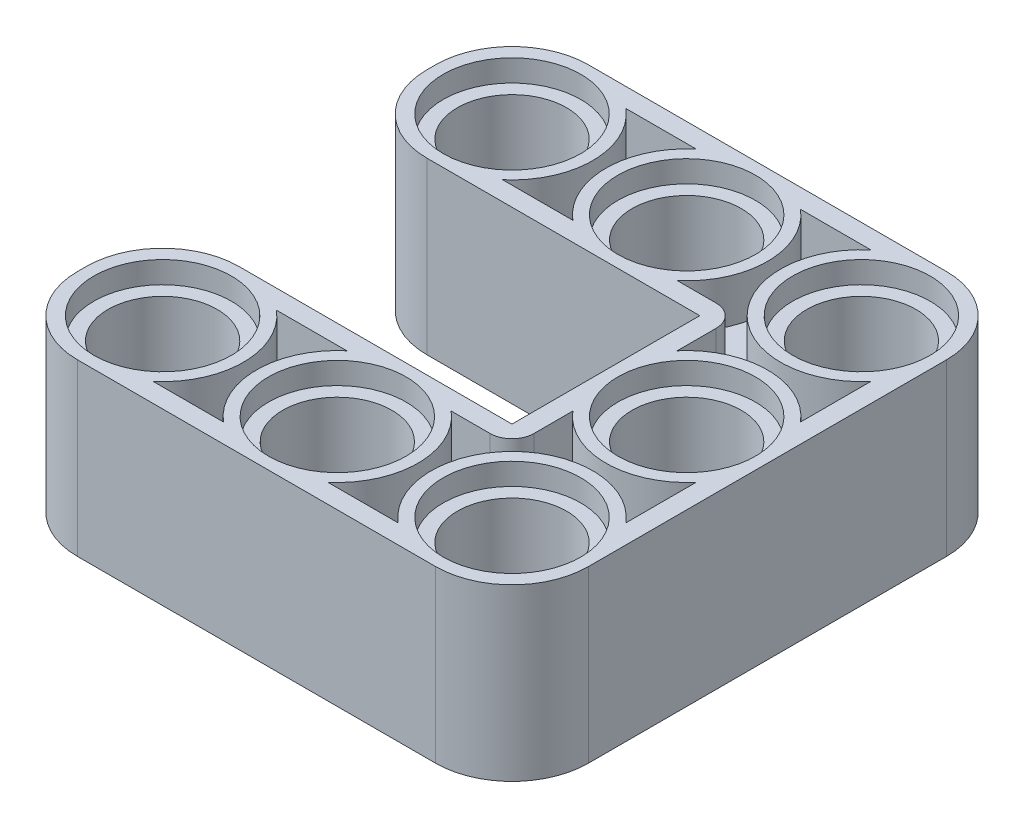
SolidWorks part; units mm, degrees
note: The reader was unsure of these and kept them because the rebuilt part matched: shared geometry of "草图1<3>", "草图1<4>", "草图1<5>", "草图3<3>", "草图3<4>", "草图3<5>".
ref_plane "前视基准面" through (0, 0, 0) normal (0, 0, 1) x (1, 0, 0)
ref_plane "上视基准面" through (0, 0, 0) normal (0, 1, 0) x (1, 0, 0)
ref_plane "右视基准面" through (0, 0, 0) normal (1, 0, 0) x (0, 0, -1)
other "Configuration Table"
sketch "草图1" plane through (0, 0, 0) normal (0, 1, 0) x (1, 0, 0)
  line L0 (-23.4, 8) -> (0, 8) construction
  line L1 (-23.4, 11.7) -> (0, 11.7)
  line L2 (-23.4, 11.7) -> (-23.4, 4.3)
  line L3 (-23.4, 4.3) -> (0, 4.3)
  line L4 (0, 11.7) -> (0, 4.3)
  line L5 (-7.4, 4.3) -> (0, 4.3)
  line L6 (-7.4, 4.3) -> (-7.4, -4.3)
  line L7 (-7.4, -4.3) -> (0, -4.3)
  line L8 (0, 4.3) -> (0, -4.3)
  line L9 (0, -4.3) -> (-23.4, -4.3)
  line L10 (0, -4.3) -> (0, -11.7)
  line L11 (0, -11.7) -> (-23.4, -11.7)
  line L12 (-23.4, -4.3) -> (-23.4, -11.7)
  line L13 (-7.4, 0) -> (0, 0) construction
  line L14 (-3.7, 0) -> (-3.7, 11.7) construction
  circle A0 centre (-3.7, 8) radius 2.5
  circle A1 centre (-3.7, 8) radius 3.15
  circle A2 centre (-3.7, 8) radius 3.7
  dimension "D5" = 7.4
  dimension "D6" = 6.3
  dimension "D7" = 5
  dimension "D1" = 8
  dimension "D2" = 23.4
  dimension "D3" = 7.4
  dimension "D4" = 23.4
extrude "凸台-拉伸1" add sketch "草图1" along normal blind 7.8 contours L9 L12 L11 L10 L7 | L8 L5 L3 L6 L7
extrude "切除-拉伸1" cut sketch "草图1<3>" along normal up to next contours A0
sketch "草图1<3>" plane through (0, 0, 0) normal (0, 1, 0) x (1, 0, 0) same geometry as "草图1"
extrude "切除-拉伸2" cut sketch "草图1<4>" along normal blind 1 contours A1 A0
sketch "草图1<4>" plane through (0, 0, 0) normal (0, 1, 0) x (1, 0, 0) same geometry as "草图1"
extrude "切除-拉伸3" cut sketch "草图1<5>" against normal blind 1 from surface at 7.8 contours A1 A0 starting at face at (-3.7, 7.8, -5.5)
sketch "草图1<5>" plane through (0, 0, 0) normal (0, 1, 0) x (1, 0, 0) same geometry as "草图1"
pattern_linear "阵列(线性)3" count 3 spacing 8 along (-1, 0, 0) of "切除-拉伸1", "切除-拉伸2", "切除-拉伸3"
pattern_linear "阵列(线性)4" count 3 spacing 8 along (0, 0, 1) of "切除-拉伸1", "切除-拉伸2", "切除-拉伸3"
pattern_linear "阵列(线性)5" count 2 spacing 16 along (0, 0, 1) of "阵列(线性)3"
sketch "草图3" plane through (0, 0, 0) normal (0, -1, 0) x (1, 0, 0)
  line L0 (-7.4, 0) -> (0, 0) construction
  line L1 (-7.4, -4.3) -> (-7.4, 4.3) construction
  line L2 (-3.7, 0) -> (-3.7, 11.7) construction
  line L3 (0, 11.7) -> (-23.4, 11.7) construction
  line L4 (-23.4, 8) -> (0, 8) construction
  line L5 (-23.4, 4.3) -> (-23.4, 11.7) construction
  line L6 (0, -11.7) -> (0, 11.7) construction
  line L7 (-3.7, 11.15) -> (-3.7, 10.5)
  line L8 (-3.7, 5.5) -> (-3.7, 4.85)
  line L9 (-3.7, 10.825) -> (-9.3106, 10.825)
  line L10 (-3.7, 5.175) -> (-9.3106, 5.175)
  line L11 (-6.85, 8) -> (-6.2, 8)
  line L12 (-1.2, 8) -> (-0.55, 8)
  line L13 (-0.875, 8) -> (-0.875, 2.3894)
  line L14 (-6.525, 8) -> (-6.525, 2.3894)
  circle A0 centre (-3.7, 8) radius 3.7
  circle A1 centre (-3.7, 8) radius 3.15
  circle A2 centre (-3.7, 8) radius 2.5
  circle A3 centre (-3.7, 0) radius 3.7
  circle A4 centre (-11.7, 8) radius 3.7
  dimension "D2" = 7.4
  dimension "D3" = 6.3
  dimension "D4" = 5
  dimension "D1" = 8
extrude "切除-拉伸4" cut sketch "草图3" against normal blind 2 contours A4 L10 L14 A0 L9 | A0 L14 L10
extrude "切除-拉伸5" cut sketch "草图3<3>" along normal blind 2 from surface at -7.8 contours A4 L10 L14 A0 L9 | A0 L14 L10 starting at face at (-11.7, 7.8, 11.15)
sketch "草图3<3>" plane through (0, 0, 0) normal (0, -1, 0) x (1, 0, 0) same geometry as "草图3"
pattern_linear "阵列(线性)6" count 2 spacing 16 along (0, 0, -1) of "切除-拉伸4", "切除-拉伸5"
extrude "切除-拉伸6" cut sketch "草图3<4>" against normal blind 2 contours A3 L13 A0 L10 L14 | A0 L14 L10
sketch "草图3<4>" plane through (0, 0, 0) normal (0, -1, 0) x (1, 0, 0) same geometry as "草图3"
extrude "切除-拉伸7" cut sketch "草图3<5>" along normal blind 2 from surface at -7.8 contours A3 L13 A0 L10 L14 | A0 L14 L10 starting at face at (-7.7, 7.8, -8)
sketch "草图3<5>" plane through (0, 0, 0) normal (0, -1, 0) x (1, 0, 0) same geometry as "草图3"
pattern_linear "阵列(线性)7" count 2 spacing 8 along (0, 0, -1) of "切除-拉伸6", "切除-拉伸7"
fillet "圆角2" radius 1 4 edges at (-6.525, 6.8, 5.175) (-6.525, 6.8, -5.175) (-6.525, 1, 5.175) (-6.525, 1, -5.175)
fillet "圆角3" radius 3.5 6 edges at (0, 3.9, 11.7) (0, 3.9, -11.7) (-23.4, 3.9, -11.7) (-23.4, 3.9, 11.7) (-23.4, 3.9, -4.3) (-23.4, 3.9, 4.3)
pattern_linear "阵列(线性)8" count 2 spacing 8 along (-1, 0, 0) of "阵列(线性)6", "切除-拉伸4", "切除-拉伸5"
